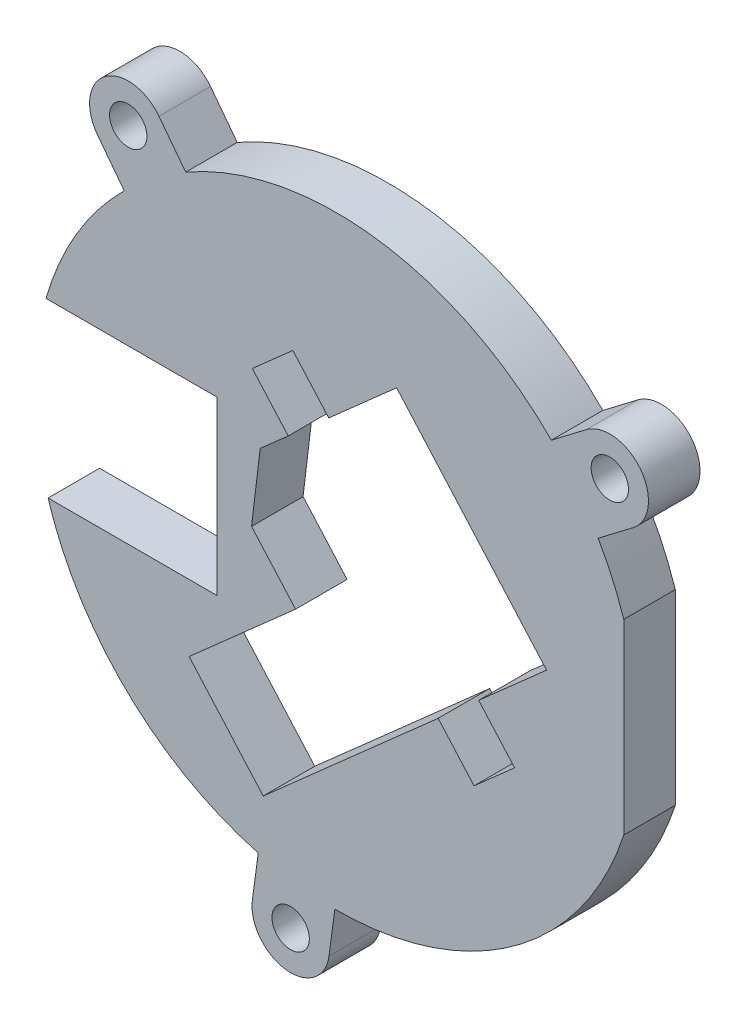
SolidWorks part; units mm, degrees
ref_plane "Front Plane" through (0, 0, 0) normal (0, 0, 1) x (1, 0, 0)
ref_plane "Top Plane" through (0, 0, 0) normal (0, 1, 0) x (1, 0, 0)
ref_plane "Right Plane" through (0, 0, 0) normal (1, 0, 0) x (0, 0, -1)
sketch "Sketch1" plane through (0, 0, 0) normal (0, 0, 1) x (1, 0, 0)
  line L0 (-21.141, 18.2245) -> (20.1141, 18.2245) construction
  line L1 (-4.8006, 1.8415) -> (-4.8006, -3.0861)
  line L2 (-4.8006, -3.0861) -> (-8.9662, -3.0861)
  line L3 (-8.9662, -3.0861) -> (-8.9662, -5.3514)
  line L4 (-8.9662, -5.3514) -> (-6.5786, -5.3514)
  line L5 (-4.9806, 7.3918) -> (-2.5835, 9.5123)
  line L6 (-2.5835, 9.5123) -> (-0.463, 7.1152)
  line L7 (-4.9806, 7.3918) -> (-2.8601, 4.9947)
  line L8 (3.2088, 10.3632) -> (-4.5153, 3.5306)
  line L9 (12.0777, 0.3371) -> (4.3536, -6.4955)
  line L10 (-4.5153, 3.5306) -> (-5.0276, -0.7207)
  line L11 (-5.0276, -0.7207) -> (0.0716, -6.4852)
  line L12 (0.0716, -6.4852) -> (4.3536, -6.4955)
  line L13 (-2.478, -3.6029) -> (7.6432, 5.3502) construction
  line L14 (3.2088, 10.3632) -> (12.0777, 0.3371)
  line L15 (3.2088, 10.3632) -> (11.8761, 18.0302)
  line L16 (-9.2588, -8.622) -> (-4.7522, -4.6355) construction
  line L17 (-9.2588, -8.622) -> (-5.994, -12.3128) construction
  line L18 (-4.7522, -4.6355) -> (-1.4874, -8.3263) construction
  line L19 (-5.994, -12.3128) -> (-1.4874, -8.3263) construction
  line L20 (12.0777, 0.3371) -> (20.228, 7.5468)
  line L21 (-6.5786, -5.3514) -> (-6.5786, -5.8039)
  line L22 (-6.5786, -5.8039) -> (-14.0208, -5.8039)
  line L23 (-14.0208, -5.8039) -> (-14.0208, 4.5593)
  line L24 (-14.0208, 4.5593) -> (-6.5786, 4.5593)
  line L25 (-6.5786, 4.5593) -> (-6.5786, 3.9924)
  line L26 (-6.5786, 3.9924) -> (-8.9662, 3.9924)
  line L27 (-8.9662, 3.9924) -> (-8.9662, 1.8415)
  line L28 (-8.9662, 1.8415) -> (-4.8006, 1.8415)
  line L29 (8.4059, -2.9109) -> (10.5264, -5.308)
  line L30 (10.5264, -5.308) -> (8.1292, -7.4285)
  line L31 (8.1292, -7.4285) -> (6.0088, -5.0313)
  line L32 (-4.7522, -4.6355) -> (-2.9639, -3.0536) construction
  line L33 (-1.4874, -8.3263) -> (0.5926, -6.4864) construction
  line L34 (-5.4555, -12.9216) -> (-0.9489, -8.9351)
  line L35 (-8.7203, -9.2308) -> (-4.2137, -5.2443)
  line L36 (-8.7203, -9.2308) -> (-5.4555, -12.9216)
  line L37 (-0.9489, -8.9351) -> (1.816, -6.4894)
  line L38 (-4.2137, -5.2443) -> (-2.4254, -3.6624)
  arc A0 (-15.2315, -0.5079) -> (3.302, 14.878) centre (0, 0) ccw construction
  circle A1 centre (0, 0) radius 21.59 construction
  circle A2 centre (0, 0) radius 21.59
  circle A3 centre (0, -18.415) radius 1.4224 construction
  circle A4 centre (0, 18.415) radius 1.4224 construction
  circle A5 centre (0, -18.415) radius 1.4224
  circle A6 centre (0, 18.415) radius 1.4224
  circle A7 centre (0, 0) radius 15.24
  dimension "D3" = 30.48
  dimension "D1" = 33.4645
  dimension "D2" = 20.0406
  dimension "D4" = 4.9276
  dimension "D5" = 2.7178
  dimension "D6" = 8.7122
  dimension "D7" = 7.8613
  dimension "D8" = 2.7178
  dimension "D9" = 3.2004
  dimension "D10" = 13.3858
  dimension "D11" = 3.1623
  dimension "D12" = 10.3124
  dimension "D13" = 8.6106
  dimension "D14" = 7.6962
  dimension "D15" = 6.0168
  dimension "D16" = 2.3876
  dimension "D17" = 4.9276
  dimension "D18" = 22.86
  dimension "D19" = 7.4422
  dimension "D20" = 5.0546
  dimension "D21" = 13.6652
  dimension "D22" = 29.2608
  dimension "D23" = 0.8128
extrude "Boss-Extrude1" add sketch "Sketch1" along normal blind 3.048 contours L15 A7 L20 L9 L29 L30 L31 L12 L33 L19 L17 L16 L32 L11 L1 L2 L3 L4 L21 L22 L23 L24 L25 L26 L27 L28 L10 L8 L7 L5 L6 | L28 L27 L26 L25 L24 L23 L22 L21 L4 L3 L2 L1 L11 L10 | A7 L15 A2 L20 A6 A5 region at (-6.8834, 2.2726, 0) region at (-10.1343, -0.6067, 0) region at (-13.5004, -8.3055, 0)
sketch "Sketch2" plane through (0, 0, 3.048) normal (0, 0, 1) x (1, 0, 0)
  line L0 (-5.0276, 2.3876) -> (-5.0276, -2.794)
  line L1 (-5.0276, 2.3876) -> (-10.4871, 2.3876)
  line L2 (-10.4871, 2.3876) -> (-10.4871, 3.8608)
  line L3 (-10.4871, 3.8608) -> (-7.085, 3.8608)
  line L4 (-7.085, 3.8608) -> (-7.085, 4.8768)
  line L5 (-7.085, 4.8768) -> (-14.4764, 4.8768)
  line L6 (-14.4764, 4.8768) -> (-14.4764, -5.2832)
  line L7 (-14.4764, -5.2832) -> (-7.085, -5.2832)
  line L8 (-7.085, -5.2832) -> (-7.085, -4.2672)
  line L9 (-7.085, -4.2672) -> (-10.4871, -4.2672)
  line L10 (-10.4871, -4.2672) -> (-10.4871, -2.794)
  line L11 (-10.4871, -2.794) -> (-5.0276, -2.794)
  line L12 (-5.0276, 2.3876) -> (-4.653, 2.3876)
  line L13 (-4.5153, 3.5306) -> (-5.0276, -0.7207) construction
  line L14 (-5.0276, -2.794) -> (-3.1935, -2.794)
  line L15 (-5.0276, -0.7207) -> (-2.4254, -3.6624) construction
  line L16 (-7.085, 3.8608) -> (-7.085, -4.2672)
  line L17 (-14.4764, 4.8768) -> (-21.032, 4.8768)
  line L18 (-14.4764, -5.2832) -> (-20.9336, -5.2832)
  arc A0 (11.8761, 18.0302) -> (20.228, 7.5468) centre (0, 0) ccw construction
  arc M2 (11.8761, 18.0302) -> (20.228, 7.5468) centre (0, 0) ccw
  dimension "D1" = 9.4488
  dimension "D2" = 7.3914
  dimension "D3" = 10.16
  dimension "D4" = 1.016
  dimension "D5" = 5.1816
  dimension "D6" = 5.4596
  dimension "D7" = 1.4732
  dimension "D8" = 1.143
extrude "Cut-Extrude3" cut sketch "Sketch2" against normal through all contours L10 L11 L0 L1 L2 L3 L4 L5 L6 L7 L8 L9 | L16 L3 L2 L1 | L16 L11 L10 L9 | L18 L6 L17 M2 region at (-11.0879, -0.2032, 3.048) region at (-8.7861, 3.1242, 3.048) region at (-8.7861, -3.5306, 3.048) region at (-17.9346, -0.1913, 3.048)
sketch "Sketch3" plane through (0, 0, 0) normal (0, 0, -1) x (-1, 0, 0)
  line L0 (-20.8712, -5.5245) -> (-16.9841, -5.5245)
  line L1 (-16.9841, -5.5245) -> (-20.8712, -5.5245) construction
  line L2 (-16.9841, -5.5245) -> (-16.9841, 4.6772)
  line L3 (-8.4059, -2.9109) -> (-20.228, 7.5468) construction
  line L4 (-16.9841, 5.5245) -> (-16.9841, -5.5245) construction
  line L5 (-16.9841, 4.6772) -> (-20.228, 7.5468)
  arc A0 (-20.228, 7.5468) -> (20.9336, -5.2832) centre (0, 0) ccw construction
  arc A1 (-20.228, 7.5468) -> (-20.8712, -5.5245) centre (0, 0) ccw
  arc A2 (-20.8712, -5.5245) -> (-20.8712, 5.5245) centre (0, 0) ccw construction
extrude "Cut-Extrude4" cut sketch "Sketch3" against normal through all
sketch "Sketch4" plane through (0, 0, 0) normal (0, 0, -1) x (-1, 0, 0)
  line L0 (-12.3201, -16.1591) -> (12.3201, 16.1591) construction
  line L1 (-13.8351, -15.0041) -> (10.8052, 17.3141)
  line L2 (-10.8052, -17.3141) -> (13.8351, 15.0041)
  line L3 (-16.1591, 12.3201) -> (16.1591, -12.3201) construction
  line L4 (-15.0041, 13.8351) -> (17.3141, -10.8052)
  line L5 (-17.3141, 10.8052) -> (15.0041, -13.8351)
  line L6 (-16.9841, 5.5245) -> (-16.9841, 4.6772)
  line L7 (-16.9841, 4.6772) -> (-12.4201, 0.64)
  line L8 (-8.4059, -2.9109) -> (-16.9841, 4.6772) construction
  line L9 (-12.4201, 0.64) -> (-3.5512, 10.6661)
  line L10 (0.463, 7.1152) -> (-11.8761, 18.0302) construction
  line L11 (-3.5512, 10.6661) -> (-8.9594, 15.4501)
  line L12 (5.0276, -0.7207) -> (2.4254, -3.6624) construction
  line L13 (0, 0) -> (2.7145, -20.1379) construction
  line L14 (1.8879, 0.2545) -> (4.6025, -19.8834)
  line L15 (-1.8879, -0.2545) -> (0.8266, -20.3924)
  line L16 (-16.1591, 12.3201) -> (12.3201, 16.1591) construction
  circle A0 centre (0, 0) radius 17.86
  arc A1 (-13.8351, -15.0041) -> (-10.8052, -17.3141) centre (-12.3201, -16.1591) ccw
  arc A2 (13.8351, 15.0041) -> (10.8052, 17.3141) centre (12.3201, 16.1591) ccw
  arc A3 (-15.0041, 13.8351) -> (-17.3141, 10.8052) centre (-16.1591, 12.3201) ccw
  arc A4 (15.0041, -13.8351) -> (17.3141, -10.8052) centre (16.1591, -12.3201) ccw
  circle A5 centre (12.3201, 16.1591) radius 1.1049
  circle A6 centre (16.1591, -12.3201) radius 1.1049
  circle A7 centre (-12.3201, -16.1591) radius 1.1049
  circle A8 centre (-16.1591, 12.3201) radius 1.1049
  arc A9 (1.8879, 0.2545) -> (-1.8879, -0.2545) centre (0, 0) ccw
  arc A10 (0.8266, -20.3924) -> (4.6025, -19.8834) centre (2.7145, -20.1379) ccw
  arc A11 (2.7145, -20.1379) -> (16.1591, -12.3201) centre (0, 0) ccw construction
  circle A12 centre (2.7145, -20.1379) radius 1.1049
  point P6 (0, 0)
  point P13 (0, 0)
  point P39 (1.3573, -10.0689)
  line M1 (-8.4059, -2.9109) -> (-16.9841, 4.6772)
  line M3 (-16.9841, -5.5245) -> (-20.8712, -5.5245)
  arc M4 (-20.8712, -5.5245) -> (20.9336, -5.2832) centre (0, 0) ccw
  line M5 (20.9336, -5.2832) -> (7.085, -5.2832)
  line M7 (7.085, 4.8768) -> (21.032, 4.8768)
  arc M8 (21.032, 4.8768) -> (-11.8761, 18.0302) centre (0, 0) ccw
  line M9 (-11.8761, 18.0302) -> (0.463, 7.1152)
  circle M24 centre (0, 18.415) radius 1.4224
  circle M25 centre (0, -18.415) radius 1.4224
  dimension "D1" = 3.81
  dimension "D2" = 3.81
  dimension "D3" = 13.97
extrude "Boss-Extrude2" add sketch "Sketch4" against normal up to vertex (3.048 mm away) contours A0 L4 L9 M9 | L4 A0 L5 L9 | L5 A0 L6 L9 M1 | L4 A3 L5 A0 A8 | A2 L1 A0 L2 A5 M8 | A0 M24 | A0 M25 | A0 L15 M25 | L15 A0 M25 | A10 M4 | A2 M8 region at (13.4131, 4.8762, 0) region at (10.9588, 8.3691, 0) region at (16.2523, 10.0852, 0) region at (0.2829, -17.4804, 0) region at (-2.9174, -21.6425, 0) region at (8.1323, 11.4955, 0) region at (-0.7535, -17.5272, 0) region at (-0.9598, -18.5708, 0) region at (-10.0849, 16.2525, 0) region at (0, 17.4932, 0) region at (-13.2407, 17.3665, 0) up to point (10.5264, -5.308, 3.048)
extrude "Cut-Extrude5" cut sketch "Sketch4<3>" against normal through all contours A4 L5 A0 L2 A1 M25 M4 | A4 A0 L4 M4 M5 | A1 L1 A0 M3 M4 | A7 | A6 | A5 | A2 L2 A0 M7 M8 | A2 A0 L1 M8 M9 M24 | L1 A1 L2 A0 A7 M4 | A10 A4 L5 A0 L14 M4 | A4 L4 A0 L5 A6 M4 | A12 region at (16.6582, -10.306, 0) region at (13.002, -14.0284, 0) region at (5.4053, -18.8788, 0) region at (-9.8123, -16.8747, 0) region at (-5.4955, 17.2518, 0) region at (-15.6105, -14.0703, 0) region at (-16.798, 10.0037, 0) region at (-18.1332, -7.9591, 0) region at (-12.3201, 16.1591, 0) region at (-16.1591, -12.3201, 0) region at (12.3201, -16.1591, 0) region at (-2.7145, -20.1379, 0)
sketch "Sketch4<3>" plane through (0, 0, 0) normal (0, 0, -1) x (-1, 0, 0) same geometry as "Sketch4"
sketch "Sketch5" plane through (0, 0, 3.048) normal (0, 0, 1) x (1, 0, 0)
  line L0 (4.3536, -6.4955) -> (-4.3384, -14.1843)
  line L1 (-4.3384, -14.1843) -> (-5.4555, -12.9216)
  line L2 (-8.7203, -9.2308) -> (-5.4555, -12.9216) construction
  line L3 (6.0088, -5.0313) -> (4.3536, -6.4955) construction
  line L4 (-5.4555, -12.9216) -> (1.816, -6.4894)
  line L5 (1.816, -6.4894) -> (4.3536, -6.4955)
extrude "Cut-Extrude10" cut sketch "Sketch5" against normal through all
sketch "Sketch6" plane through (0, 0, 3.048) normal (0, 0, 1) x (1, 0, 0)
  line L0 (17.3141, 10.8052) -> (15.2768, 9.2519) construction
  line L1 (15.0041, 13.8351) -> (12.9668, 12.2818) construction
  line L2 (17.3141, 10.8052) -> (15.2768, 9.2519)
  line L3 (15.0041, 13.8351) -> (12.9668, 12.2818)
  line L4 (17.5451, 10.5023) -> (15.472, 8.9216)
  line L5 (14.7731, 14.138) -> (12.7, 12.5574)
  line L23 (-4.9801, -19.8325) -> (-4.6378, -17.2935)
  line L24 (-0.1068, -17.9043) -> (-0.449, -20.4433)
  line L25 (-4.9801, -19.8325) -> (-4.6318, -17.2489)
  line L26 (-0.1008, -17.8597) -> (-0.449, -20.4433)
  line L29 (14.7731, 14.138) -> (12.7358, 12.5847) construction
  line L30 (17.5451, 10.5023) -> (15.5078, 8.9489) construction
  line L31 (-14.138, 14.7731) -> (-12.5847, 12.7358)
  line L32 (-8.9489, 15.5078) -> (-10.5023, 17.5451)
  line L33 (-14.138, 14.7731) -> (-12.5574, 12.7)
  line L34 (-8.9216, 15.472) -> (-10.5023, 17.5451)
  arc A0 (17.3141, 10.8052) -> (15.0041, 13.8351) centre (16.1591, 12.3201) ccw construction
  arc A1 (17.3141, 10.8052) -> (15.0041, 13.8351) centre (16.1591, 12.3201) ccw
  arc A2 (17.5451, 10.5023) -> (14.7731, 14.138) centre (16.1591, 12.3201) ccw
  arc A11 (-4.9801, -19.8325) -> (-0.449, -20.4433) centre (-2.7145, -20.1379) ccw
  arc A12 (-4.9801, -19.8325) -> (-0.449, -20.4433) centre (-2.7145, -20.1379) ccw
  circle A14 centre (0, 0) radius 17.86
  arc A15 (-10.5023, 17.5451) -> (-14.138, 14.7731) centre (-12.3201, 16.1591) ccw
  arc A16 (-10.5023, 17.5451) -> (-14.138, 14.7731) centre (-12.3201, 16.1591) ccw
  line M25 (-4.2602, -17.3444) -> (-4.6025, -19.8834)
  arc M26 (-4.6025, -19.8834) -> (-0.8266, -20.3924) centre (-2.7145, -20.1379) ccw
  line M27 (-0.8266, -20.3924) -> (-0.4844, -17.8534)
  arc M28 (-0.4844, -17.8534) -> (16.9841, -5.5245) centre (0, 0) ccw
  arc M30 (16.9841, 5.5245) -> (15.2768, 9.2519) centre (0, 0) ccw
  line M31 (15.2768, 9.2519) -> (17.3141, 10.8052)
  arc M32 (17.3141, 10.8052) -> (15.0041, 13.8351) centre (16.1591, 12.3201) ccw
  line M33 (15.0041, 13.8351) -> (12.9668, 12.2818)
  arc M34 (12.9668, 12.2818) -> (-9.2519, 15.2768) centre (0, 0) ccw
  line M35 (-9.2519, 15.2768) -> (-10.8052, 17.3141)
  arc M36 (-10.8052, 17.3141) -> (-13.8351, 15.0041) centre (-12.3201, 16.1591) ccw
  line M37 (-13.8351, 15.0041) -> (-12.2818, 12.9668)
  arc M38 (-12.2818, 12.9668) -> (-17.1812, 4.8768) centre (0, 0) ccw
  arc M42 (-17.0607, -5.2832) -> (-4.2602, -17.3444) centre (0, 0) ccw
  dimension "D1" = 0.381
  dimension "D2" = 0.381
  dimension "D3" = 0.381
extrude "Boss-Extrude3" add sketch "Sketch6" against normal up to vertex contours L34 A16 L33 M38 M37 M36 M35 M34 | L25 A12 L26 M28 M27 M26 M25 M42 | L4 A2 L5 M34 M33 M32 M31 M30 region at (17.7383, 13.5242, 3.048) region at (-9.1284, 15.4449, 3.048) region at (-0.1744, -17.8725, 3.048) up to point (8.4059, -2.9109, 0)
